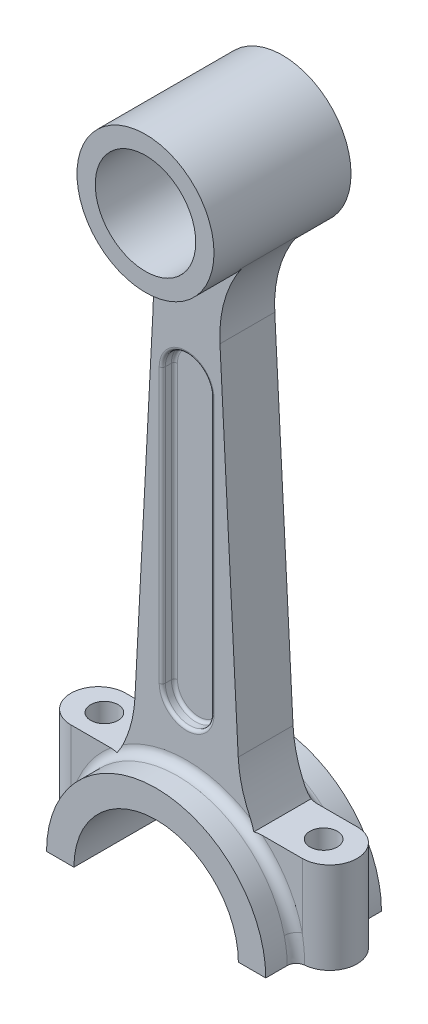
SolidWorks part; units mm, degrees
ref_plane "Front Plane" through (0, 0, 0) normal (0, 0, 1) x (1, 0, 0)
ref_plane "Top Plane" through (0, 0, 0) normal (0, 1, 0) x (1, 0, 0)
ref_plane "Right Plane" through (0, 0, 0) normal (1, 0, 0) x (0, 0, -1)
sketch "Sketch1" plane through (0, 0, 0) normal (0, 0, 1) x (1, 0, 0)
  line L0 (0, 0) -> (0, -4424.68) construction
  line L1 (-254, -511.9534) -> (-453.3823, -4316.3945)
  line L2 (254, -511.9534) -> (453.3823, -4316.3945)
  line L3 (-453.3823, -4316.3945) -> (453.3823, -4316.3945)
  line L4 (-254, -511.9534) -> (254, -511.9534)
  line L5 (-914.4, -5110.48) -> (-685.8, -5110.48)
  line L6 (685.8, -5110.48) -> (914.4, -5110.48)
  circle A0 centre (0, 0) radius 571.5
  circle A1 centre (0, 0) radius 419.1
  arc A2 (685.8, -5110.48) -> (-685.8, -5110.48) centre (0, -5110.48) ccw
  arc A3 (914.4, -5110.48) -> (-914.4, -5110.48) centre (0, -5110.48) ccw
  dimension "D1" = 1143
  dimension "D2" = 838.2
  dimension "D3" = 1371.6
  dimension "D4" = 1828.8
  dimension "D5" = 5110.48
  dimension "D6" = 508
  dimension "D7" = 6
extrude "Boss-Extrude1" add sketch "Sketch1" along normal mid plane 1143 contours A3 L5 | A2 | A0 | A1
extrude "Boss-Extrude2" add sketch "Sketch1<3>" along normal mid plane 457.2 contours L2 L3 L1 L4
sketch "Sketch1<3>" plane through (0, 0, 0) normal (0, 0, 1) x (1, 0, 0) same geometry as "Sketch1"
sketch "Sketch5" plane through (0, 0, 228.6) normal (0, 0, 1) x (1, 0, 0)
  line L0 (0, 0) -> (0, -5073.259) construction
  line L1 (0, -3679.6295) -> (0, -1393.6295) construction
  line L2 (-203.2, -3679.6295) -> (-203.2, -1393.6295)
  line L3 (203.2, -3679.6295) -> (203.2, -1393.6295)
  arc A0 (-203.2, -3679.6295) -> (203.2, -3679.6295) centre (0, -3679.6295) ccw
  arc A1 (203.2, -1393.6295) -> (-203.2, -1393.6295) centre (0, -1393.6295) ccw
  point P5 (0, -2536.6295)
  dimension "D2" = 203.2
  dimension "D1" = 2286
extrude "Cut-Extrude2" cut sketch "Sketch5" against normal blind 101.6
mirror "Mirror2" about plane through (0, 0, 0) normal (0, 0, 1) of "Cut-Extrude2"
fillet "Fillet1" radius 25.4 16 edges at (0, -1190.4295, -228.6) (203.2, -2536.6295, -228.6) (0, -3882.8295, -228.6) (0, -1190.4295, -127) (203.2, -2536.6295, -127) (0, -3882.8295, -127) (0, -1190.4295, 228.6) (203.2, -2536.6295, 228.6) (0, -3882.8295, 228.6) (0, -1190.4295, 127) (203.2, -2536.6295, 127) (0, -3882.8295, 127) (-203.2, -2536.6295, -228.6) (-203.2, -2536.6295, -127) (-203.2, -2536.6295, 228.6) (-203.2, -2536.6295, 127)
extrude "Boss-Extrude5" add sketch "Sketch1<5>" along normal mid plane 965.2 contours A3 L5 A2 L6
sketch "Sketch1<5>" plane through (0, 0, 0) normal (0, 0, 1) x (1, 0, 0) same geometry as "Sketch1"
ref_plane "Plane1" through (0, -4348.48, 0) normal (0, -1, 0) x (-1, 0, 0)
fillet "Fillet3" radius 1016 4 edges at (-254, -511.9534, 0) (254, -511.9534, 0) (453.3823, -4316.3945, 0) (-453.3823, -4316.3945, 0)
sketch "Sketch8" plane through (0, -4348.48, 0) normal (0, -1, 0) x (-1, 0, 0)
  line L0 (965.2, 0) -> (-965.2, 0) construction
  line L1 (-685.8, 0) -> (-914.4, 0) construction
  line L2 (965.2, -228.6) -> (-965.2, -228.6)
  line L3 (965.2, 228.6) -> (-965.2, 228.6)
  arc A0 (965.2, -228.6) -> (965.2, 228.6) centre (965.2, 0) ccw
  arc A1 (-965.2, 228.6) -> (-965.2, -228.6) centre (-965.2, 0) ccw
  point P5 (0, 0)
  dimension "D2" = 228.6
  dimension "D1" = 1930.4
extrude "Boss-Extrude6" add sketch "Sketch8" along normal up to surface (762 mm away) up to face at (-800.1, -5110.48, 0)
ref_plane "Plane2" through (-685.8, -5110.48, -228.6) normal (-1, 0, 0) x (0, 0, 1)
sketch "Sketch14" plane through (0, 0, -228.6) normal (0, 0, -1) x (-1, 0, 0)
  line L1 (-685.8, -5110.48) -> (685.8, -5110.48)
  line L2 (-685.8, -5110.48) -> (685.8, -5110.48)
  arc A1 (685.8, -5110.48) -> (-685.8, -5110.48) centre (0, -5110.48) ccw
  arc A2 (685.8, -5110.48) -> (-685.8, -5110.48) centre (0, -5110.48) ccw
  dimension "D1" = 0
extrude "Cut-Extrude3" cut sketch "Sketch14" against normal through all
sketch "Sketch15" plane through (0, -4348.48, 0) normal (0, 1, 0) x (1, 0, 0)
  line L0 (-914.4, 0) -> (-685.8, 0) construction
  line L1 (685.8, 0) -> (914.4, 0) construction
  circle A0 centre (-914.4, 0) radius 114.3
  circle A1 centre (914.4, 0) radius 114.3
  dimension "D1" = 228.6
  dimension "D2" = 228.6
extrude "Cut-Extrude4" cut sketch "Sketch15" against normal through all
fillet "Fillet4" radius 76.2 2 edges at (0, -4196.08, 228.6) (0, -4196.08, -228.6)
